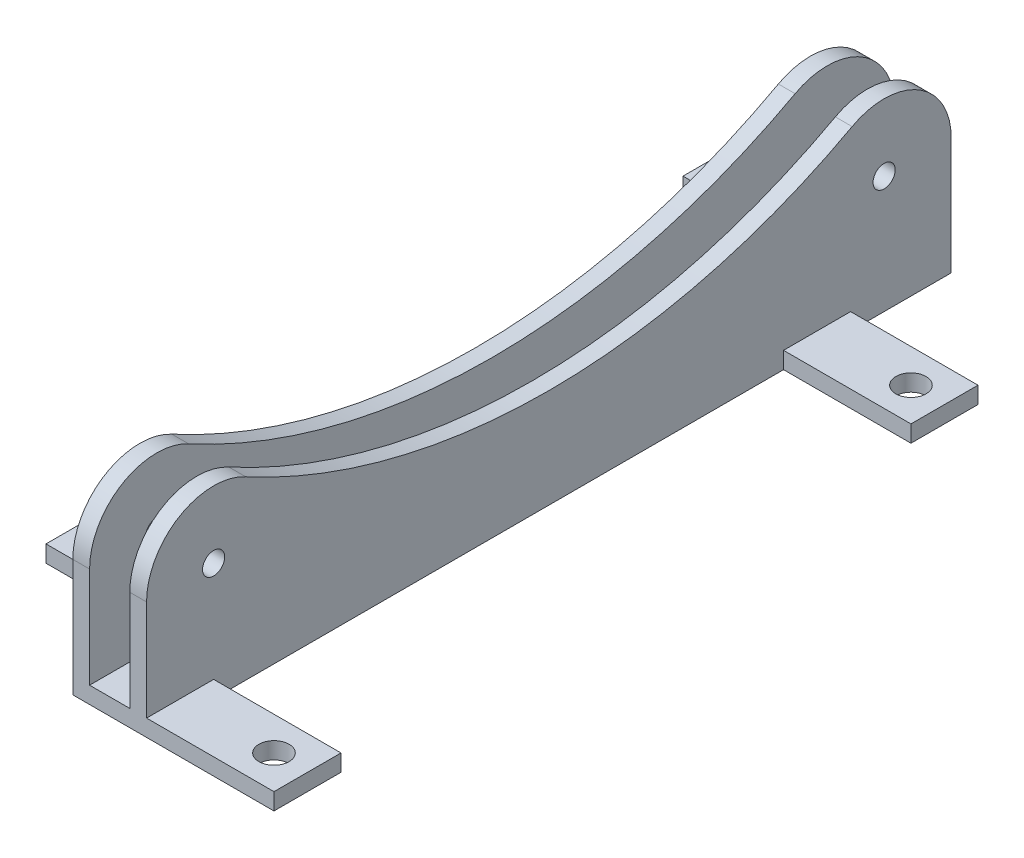
SolidWorks part; units mm, degrees
ref_plane "Front Plane" through (0, 0, 0) normal (0, 0, 1) x (1, 0, 0)
ref_plane "Top Plane" through (0, 0, 0) normal (0, 1, 0) x (1, 0, 0)
ref_plane "Right Plane" through (0, 0, 0) normal (1, 0, 0) x (0, 0, -1)
sketch "Sketch1" plane through (0, 0, 0) normal (1, 0, 0) x (0, 0, -1)
  line L0 (-50, 17.5) -> (50, 17.5) construction
  line L1 (0, 0) -> (0, 109.5465) construction
  line L2 (-60, 0) -> (60, 0)
  line L3 (-60, -0.0194) -> (-60, 17.5)
  line L4 (60, 17.5) -> (60, 0)
  circle A0 centre (0, 109.5465) radius 100 construction
  circle A1 centre (-50, 17.5) radius 4.75 construction
  circle A2 centre (50, 17.5) radius 4.75 construction
  arc A3 (-45.2267, 26.2873) -> (-60, 17.5) centre (-50, 17.5) ccw
  arc A4 (60, 17.5) -> (45.2267, 26.2873) centre (50, 17.5) ccw
  arc A5 (-45.2267, 26.2873) -> (45.2267, 26.2873) centre (0, 109.5465) ccw
  point P11 (0, 0)
  dimension "D1" = 200
  dimension "D2" = 9.5
  dimension "D5" = 10
  dimension "D3" = 100
  dimension "D4" = 17.5
extrude "Boss-Extrude1" add sketch "Sketch1" along normal blind 2.5 contours A5 A3 L3 L2 L4 A4 region at (0, 10.6614, 0)
extrude "Boss-Extrude2" add sketch "Sketch1<2>" against normal blind 2.5 from offset 6 separate body contours A5 A3 L3 L2 L4 A4 region at (0, 10.6614, 0) offset against normal yes
sketch "Sketch1<2>" plane through (0, 0, 0) normal (1, 0, 0) x (0, 0, -1) same geometry as "Sketch1"
sketch "Sketch4" plane through (0, 0, 0) normal (-1, 0, 0) x (0, 0, 1)
  line L1 (60, 0) -> (60, 17.5) construction
  line L5 (-60, 0) -> (60, 0)
  line L6 (-60, 0) -> (-60, 2.5)
  line L7 (-60, 2.5) -> (60, 2.5)
  line L8 (60, 0) -> (60, 2.5)
  line L9 (-60, 0) -> (60, 2.5) construction
  line L10 (-60, 2.5) -> (60, 0) construction
  point P4 (0, 1.25)
  dimension "D1" = 2.5
extrude "Boss-Extrude3" add sketch "Sketch4" along normal up to next
hole_wizard "M4x0.7 Tapped Hole1" positions "Sketch2" profile "Sketch3" tap size "M4x0.7" standard "ANSI Metric" end condition through all
sketch "Sketch2" plane through (2.5, 0, 0) normal (-1, 0, 0) x (0, 0, 1)
  point P0 (-50, 17.5)
  point P3 (50, 17.5)
sketch "Sketch3" plane through (2.5, 17.5, -50) normal (0, 1, 0) x (0, 0, -1)
  line L0 (0, 0) -> (0, 11)
  line L1 (0, 11) -> (1.65, 11)
  line L2 (1.65, 11) -> (1.65, 0)
  line L5 (1.65, 0) -> (0, 0)
  line L11 (0, -6.35) -> (0, 107.95) construction
  dimension "Thru Tap Drill Dia." = 3.3
  dimension "Thru Tap Drill Depth" = 11
cosmetic thread "Hole Thread1" parameters "D1"=11, "D2"=4
cosmetic thread "Hole Thread2" parameters "D1"=11, "D2"=4
sketch "Sketch5" plane through (0, 0, 0) normal (0, -1, 0) x (1, 0, 0)
  line L1 (2.5, 45) -> (-27.5, 45)
  line L2 (2.5, 45) -> (2.5, 35)
  line L3 (2.5, 35) -> (-27.5, 35)
  line L4 (-27.5, 45) -> (-27.5, 35)
  line L5 (2.5, 45) -> (-27.5, 35) construction
  line L6 (2.5, 35) -> (-27.5, 45) construction
  line L7 (2.5, -60) -> (-27.5, -60)
  line L8 (2.5, -60) -> (2.5, -50)
  line L9 (2.5, -50) -> (-27.5, -50)
  line L10 (-27.5, -60) -> (-27.5, -50)
  line L11 (2.5, -60) -> (-27.5, -50) construction
  line L12 (2.5, -50) -> (-27.5, -60) construction
  line L15 (-8.5, 60) -> (21.5, 60)
  line L16 (-8.5, 60) -> (-8.5, 50)
  line L17 (-8.5, 50) -> (21.5, 50)
  line L18 (21.5, 60) -> (21.5, 50)
  line L19 (-8.5, 60) -> (21.5, 50) construction
  line L20 (-8.5, 50) -> (21.5, 60) construction
  line L21 (-8.5, -35) -> (21.5, -35)
  line L22 (-8.5, -35) -> (-8.5, -45)
  line L23 (-8.5, -45) -> (21.5, -45)
  line L24 (21.5, -35) -> (21.5, -45)
  line L25 (-8.5, -35) -> (21.5, -45) construction
  line L26 (-8.5, -45) -> (21.5, -35) construction
  line L27 (2.5, 60) -> (2.5, -60) construction
  line L28 (-8.5, 60) -> (-8.5, -60) construction
  point P4 (-12.5, 40)
  point P5 (-8.5, 60)
  point P10 (-12.5, -55)
  point P13 (2.5, 45)
  point P16 (-8.5, -27.5704)
  point P21 (6.5, 55)
  point P26 (6.5, -40)
  point P30 (2.5, -60)
  dimension "D1" = 10
  dimension "D2" = 5
  dimension "D3" = 30
  dimension "D4" = 10
  dimension "D5" = 5
extrude "Boss-Extrude4" add sketch "Sketch5" against normal blind 2.5
hole_wizard "Ø4.5 (4.5) Diameter Hole1" positions "Sketch6" profile "Sketch7" hole size "Ø4.5" standard "ANSI Metric" end condition through all
sketch "Sketch6" plane through (0, 2.5, 0) normal (0, 1, 0) x (1, 0, 0)
  line L0 (-27.5, 55) -> (-22.5, 55) construction
  line L1 (-27.5, 50) -> (-27.5, 60) construction
  line L2 (-22.5, 55) -> (-22.5, 50) construction
  line L3 (-8.5, 50) -> (-27.5, 50) construction
  line L6 (-22.5, -35) -> (-22.5, -40) construction
  line L7 (-27.5, -35) -> (-8.5, -35) construction
  line L8 (-22.5, -40) -> (-27.5, -40) construction
  line L9 (-27.5, -45) -> (-27.5, -35) construction
  line L12 (16.5, 40) -> (21.5, 40) construction
  line L13 (21.5, 45) -> (21.5, 35) construction
  line L16 (16.5, 40) -> (16.5, 35) construction
  line L17 (21.5, 35) -> (2.5, 35) construction
  line L20 (16.5, -55) -> (21.5, -55) construction
  line L21 (21.5, -50) -> (21.5, -60) construction
  line L24 (16.5, -55) -> (16.5, -50) construction
  line L25 (2.5, -50) -> (21.5, -50) construction
  point P0 (-22.5, 55)
  point P2 (16.5, 40)
  point P4 (16.5, -55)
  point P6 (-22.5, -40)
sketch "Sketch7" plane through (-22.5, 2.5, -55) normal (1, 0, 0) x (0, 0, 1)
  line L0 (0, 0) -> (0, 2.5)
  line L1 (0, 2.5) -> (2.25, 2.5)
  line L2 (2.25, 2.5) -> (2.25, 0)
  line L5 (2.25, 0) -> (0, 0)
  line L11 (0, -6.35) -> (0, 107.95) construction
  dimension "Thru Hole Dia." = 4.5
  dimension "Thru Hole Depth" = 2.5
